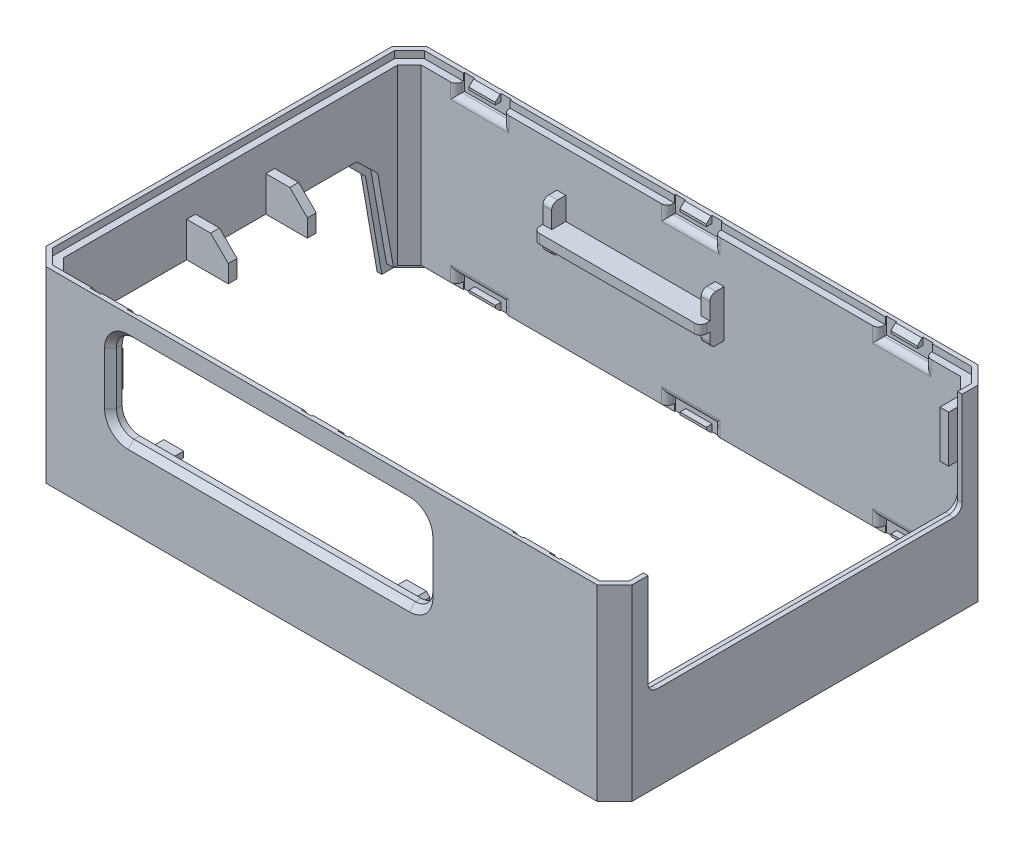
SolidWorks part; units mm, degrees
ref_plane "前视基准面" through (0, 0, 0) normal (0, 0, 1) x (1, 0, 0)
ref_plane "上视基准面" through (0, 0, 0) normal (0, 1, 0) x (1, 0, 0)
ref_plane "右视基准面" through (0, 0, 0) normal (1, 0, 0) x (0, 0, -1)
sketch "草图1" plane through (0, 0, 0) normal (0, 1, 0) x (1, 0, 0)
  line L1 (-50, 32.5) -> (50, 32.5)
  line L2 (-50, 32.5) -> (-50, -32.5)
  line L3 (-50, -32.5) -> (50, -32.5)
  line L4 (50, 32.5) -> (50, -32.5)
  line L5 (-50, 32.5) -> (50, -32.5) construction
  line L6 (-50, -32.5) -> (50, 32.5) construction
  point P0 (0, 0)
  dimension "D1" = 65
  dimension "D2" = 100
extrude "凸台-拉伸1" add sketch "草图1" along normal blind 32
sketch "草图2" plane through (0, 32, 0) normal (0, 1, 0) x (1, 0, 0)
  line L8 (48, -30.5) -> (48, 30.5)
  line L9 (48, 30.5) -> (-48, 30.5)
  line L10 (-48, 30.5) -> (-48, -30.5)
  line L11 (-48, -30.5) -> (48, -30.5)
  line L12 (48, -30.5) -> (48, 30.5)
  line L13 (48, 30.5) -> (-48, 30.5)
  line L14 (-48, 30.5) -> (-48, -30.5)
  line L15 (-48, -30.5) -> (48, -30.5)
  dimension "D1" = 2
extrude "切除-拉伸1" cut sketch "草图2" against normal through all
sketch "草图4" plane through (-50, 0, 0) normal (-1, 0, 0) x (0, 0, 1)
  line L0 (-32.5, 0) -> (32.5, 0) construction
  line L3 (-28, 0) -> (28, 0)
  line L7 (-25.0863, 16.5) -> (-21.5, 20)
  line L8 (21.5, 20) -> (25.09, 16.5)
  line L9 (32.5, 32) -> (32.5, 0) construction
  line L12 (-25.0863, 16.5) -> (-28, 0)
  line L13 (-21.5, 20) -> (21.5, 20)
  line L14 (25.09, 16.5) -> (28, 0)
  line L15 (-32.5, 0) -> (32.5, 0) construction
  line L16 (-32.5, 32) -> (-32.5, 0) construction
  dimension "D1" = 16.5
  dimension "D2" = 20
  dimension "D3" = 4.5
  dimension "D4" = 4.5
  dimension "D5" = 11
  dimension "D6" = 11
  dimension "D7" = 7.4137
  dimension "D8" = 7.41
extrude "切除-拉伸2" cut sketch "草图4" against normal blind 2
sketch "草图7" plane through (0, 0, 32.5) normal (0, 0, 1) x (1, 0, 0)
  line L0 (-50, 32) -> (-50, 0) construction
  line L5 (-50, 32) -> (50, 32) construction
  line L16 (-36, 28) -> (-36, 13)
  line L17 (18, 28) -> (-36, 28)
  line L18 (18, 13) -> (18, 28)
  line L19 (-36, 13) -> (18, 13)
  dimension "D1" = 54
  dimension "D2" = 15
  dimension "D3" = 14
  dimension "D4" = 4
extrude "切除-拉伸3" cut sketch "草图7" against normal blind 2.5
fillet "圆角7" radius 3 4 edges at (-36, 28, 31.5) (18, 28, 31.5) (18, 13, 31.5) (-36, 13, 31.5)
chamfer "倒角1" distance 1 angle 45 8 edges at (-9, 28, 32.5) (-35.1213, 27.1213, 32.5) (17.1213, 27.1213, 32.5) (-36, 20.5, 32.5) (18, 20.5, 32.5) (-35.1213, 13.8787, 32.5) (17.1213, 13.8787, 32.5) (-9, 13, 32.5)
ref_plane "基准面4" through (0, 19.25, 0) normal (0, -1, 0) x (-1, 0, 0)
sketch "草图17" plane through (-48, 0, 0) normal (1, 0, 0) x (0, 0, -1)
  line L1 (-6, 20) -> (-7.5, 20)
  line L2 (-6, 20) -> (-6, 26)
  line L3 (-6, 26) -> (-7.5, 26)
  line L4 (-7.5, 20) -> (-7.5, 26)
  line L5 (32.5, 32) -> (32.5, 0) construction
  line L6 (6, 20) -> (7.5, 20)
  line L7 (6, 20) -> (6, 26)
  line L8 (6, 26) -> (7.5, 26)
  line L9 (7.5, 20) -> (7.5, 26)
  line L10 (-21.5, 20) -> (21.5, 20) construction
  line L12 (-32.5, 32) -> (-32.5, 0) construction
  dimension "D1" = 1.5
  dimension "D2" = 1.5
  dimension "D3" = 25
  dimension "D4" = 25
  dimension "D5" = 6
extrude "凸台-拉伸6" add sketch "草图17" along normal blind 7.1
chamfer "倒角6" distance 3 angle 45 2 edges at (-40.9, 26, -6.75) (-40.9, 26, 6.75)
chamfer "倒角7" distance 2 angle 45 4 edges at (-48, 16, -30.5) (-48, 16, 30.5) (48, 16, -30.5) (48, 16, 30.5)
chamfer "倒角8" distance 3 angle 45 4 edges at (-50, 16, 32.5) (-50, 16, -32.5) (50, 16, -32.5) (50, 16, 32.5)
sketch "草图28" plane through (-50, 0, 0) normal (-1, 0, 0) x (0, 0, 1)
  line L27 (-29.3, 22.3393) -> (-29.3, 0)
  line L28 (-29.3, 0) -> (-26.9872, 0)
  line L29 (-26.9872, 0) -> (-24.2154, 15.8784)
  line L30 (-24.2154, 15.8784) -> (-21.1176, 18.9896)
  line L31 (-21.1176, 18.9896) -> (21.1176, 18.9896)
  line L32 (21.1176, 18.9896) -> (24.2152, 15.8784)
  line L33 (24.2152, 15.8784) -> (27.008, 0)
  line L34 (27.008, 0) -> (29.3, 0)
  line L35 (29.3, 0) -> (29.3, 22.3393)
  line L36 (29.3, 22.3393) -> (-29.3, 22.3393)
  line L37 (28.5, 0) -> (-28.5, 0) construction
  line L38 (-29.5, 0) -> (-28, 0) construction
  line L39 (28, 0) -> (29.5, 0) construction
extrude "凸台-拉伸13" add sketch "草图28" against normal blind 0.8
sketch "草图35" plane through (48, 0, 0) normal (-1, 0, 0) x (0, 0, 1)
  line L0 (-28, 32) -> (28, 32)
  line L1 (-28, 32) -> (-28, 14)
  line L2 (-28, 14) -> (28, 14)
  line L3 (28, 32) -> (28, 14)
  line L4 (32.5, 0) -> (32.5, 32) construction
  line L5 (-32.5, 32) -> (-32.5, 0) construction
  line L6 (28.5, 32) -> (-28.5, 32) construction
  dimension "D1" = 18
  dimension "D3" = 4.5
  dimension "D4" = 4.5
extrude "切除-拉伸6" cut sketch "草图35" against normal blind 1.2
fillet "圆角17" radius 2 2 edges at (48.6, 14, -28) (48.6, 14, 28)
sketch "草图39" plane through (49.2, 0, 0) normal (-1, 0, 0) x (0, 0, 1)
  line L0 (32.5, 0) -> (32.5, 32) construction
  line L1 (-32.5, 32) -> (-32.5, 0) construction
  line L2 (28, 32) -> (-28, 32) construction
  line L3 (29.5, 32) -> (-29.5, 32) construction
  line L4 (29.5, 0) -> (-29.5, 0) construction
  line L12 (-26.8, 32) -> (-26.8, 16)
  line L13 (-25.3, 14.5) -> (25.3, 14.5)
  line L14 (26.8, 16) -> (26.8, 32)
  line L15 (26.8, 32) -> (-26.8, 32)
  arc A6 (-26.8, 16) -> (-25.3, 14.5) centre (-25.3, 16) ccw
  arc A7 (25.3, 14.5) -> (26.8, 16) centre (25.3, 16) ccw
  dimension "D1" = 7.2
  dimension "D2" = 7.2
  dimension "D3" = 16
  dimension "D4" = 14.5
extrude "切除-拉伸7" cut sketch "草图39" against normal blind 1.2
ref_plane "基准面5" through (-50, 32, 29.5) normal (0.7071, 0, 0.7071) x (0.7071, 0, -0.7071)
sketch "草图44" plane through (0, 0, -28) normal (0, 0, 1) x (1, 0, 0)
  line L0 (48, 32) -> (48, 16) construction
  line L1 (48, 28.5) -> (46.5, 28.5)
  line L2 (48, 28.5) -> (48, 20.5)
  line L3 (48, 20.5) -> (46.5, 20.5)
  line L4 (46.5, 28.5) -> (46.5, 20.5)
  line L5 (50, 14.5) -> (49.2, 14.5) construction
  dimension "D1" = 1.5
  dimension "D2" = 8
  dimension "D3" = 6
extrude "凸台-拉伸15" add sketch "草图44" along normal blind 1.5 and the other way up to surface (2.5 mm away) other way up to face at (0, 16, -30.5)
sketch "草图45" plane through (0, 0, 28) normal (0, 0, -1) x (-1, 0, 0)
  line L4 (-48, 28.5) -> (-48, 20.5)
  line L5 (-46.5, 28.5) -> (-48, 28.5)
  line L6 (-46.5, 20.5) -> (-46.5, 28.5)
  line L7 (-48, 20.5) -> (-46.5, 20.5)
  line L8 (-48, 28.5) -> (-48, 20.5)
  line L9 (-46.5, 28.5) -> (-48, 28.5)
  line L10 (-46.5, 20.5) -> (-46.5, 28.5)
  line L11 (-48, 20.5) -> (-46.5, 20.5)
  dimension "D1" = 0
extrude "凸台-拉伸16" add sketch "草图45" along normal blind 1.5 and the other way up to surface (2.5 mm away) other way up to face at (-9, 20.5, 30.5)
ref_plane "基准面6" through (48, 0, -28.5) normal (0, 0, -1) x (-1, 0, 0)
sketch "草图48" plane through (0, 32, 0) normal (0, 1, 0) x (1, 0, 0)
  line L31 (49.2, 29.1686) -> (49.2, -29.1686)
  line L32 (46.6686, -31.7) -> (49.2, -29.1686)
  line L33 (-46.6686, -31.7) -> (46.6686, -31.7)
  line L34 (-49.2, -29.1686) -> (-46.6686, -31.7)
  line L35 (-49.2, 29.1686) -> (-49.2, -29.1686)
  line L36 (-46.6686, 31.7) -> (-49.2, 29.1686)
  line L37 (46.6686, 31.7) -> (-46.6686, 31.7)
  line L38 (49.2, 29.1686) -> (46.6686, 31.7)
  point P0 (48, 30.5)
  point P1 (-48, -30.5)
  point P2 (48, -30.5)
  point P3 (-48, 30.5)
extrude "切除-拉伸8" cut sketch "草图48" against normal blind 1.2
sketch "草图57" plane through (0, 0, 30.5) normal (0, 0, -1) x (-1, 0, 0)
  line L1 (-21.2, 16) -> (-22.7, 16)
  line L2 (-21.2, 16) -> (-21.2, 22)
  line L3 (-21.2, 22) -> (-22.7, 22)
  line L4 (-22.7, 16) -> (-22.7, 22)
  line L5 (39.4, 16) -> (40.9, 16)
  line L6 (39.4, 16) -> (39.4, 22)
  line L7 (39.4, 22) -> (40.9, 22)
  line L8 (40.9, 16) -> (40.9, 22)
  line L9 (47, 32) -> (-47, 32) construction
  line L10 (-50, 32) -> (-50, 0) construction
  line L11 (50, 0) -> (50, 32) construction
  line L12 (46, 0) -> (-46, 0) construction
  line L17 (-14, 12) -> (-10, 12)
  line L18 (-14, 12) -> (-14, 11)
  line L19 (-14, 11) -> (-10, 11)
  line L20 (-10, 12) -> (-10, 11)
  line L21 (28, 12) -> (32, 12)
  line L22 (28, 12) -> (28, 11)
  line L23 (28, 11) -> (32, 11)
  line L24 (32, 12) -> (32, 11)
  dimension "D1" = 1.5
  dimension "D2" = 16
  dimension "D3" = 28.8
  dimension "D4" = 10.6
  dimension "D5" = 4
  dimension "D6" = 4
  dimension "D7" = 1
  dimension "D8" = 1
  dimension "D9" = 12
  dimension "D10" = 18
  dimension "D11" = 60
  dimension "D12" = 6
extrude "凸台-拉伸27" add sketch "草图57" along normal blind 2.5
sketch "草图60" plane through (21.2, 0, 0) normal (-1, 0, 0) x (0, 0, 1)
  line L0 (28, 22) -> (30.5, 22) construction
  line L1 (28, 22) -> (29.25, 22)
  line L2 (28, 22) -> (28, 16)
  line L3 (28, 16) -> (29.25, 16)
  line L4 (29.25, 22) -> (29.25, 16)
  line L5 (28, 16) -> (30.5, 16) construction
  dimension "D1" = 1.25
extrude "凸台-拉伸28" add sketch "草图60" along normal blind 1
sketch "草图61" plane through (-39.4, 0, 0) normal (1, 0, 0) x (0, 0, -1)
  line L4 (-28, 16) -> (-28, 22)
  line L5 (-29.25, 16) -> (-28, 16)
  line L6 (-29.25, 22) -> (-29.25, 16)
  line L7 (-28, 22) -> (-29.25, 22)
  line L8 (-28, 16) -> (-28, 22)
  line L9 (-29.25, 16) -> (-28, 16)
  line L10 (-29.25, 22) -> (-29.25, 16)
  line L11 (-28, 22) -> (-29.25, 22)
  dimension "D1" = 0
extrude "凸台-拉伸29" add sketch "草图61" along normal blind 1
chamfer "倒角16" distance 0.6 angle 45 2 edges at (14, 12, 29.25) (-32, 12, 29.25)
sketch "草图62" plane through (0, 0, 0) normal (0, -1, 0) x (1, 0, 0)
  line L15 (-49.2, 28.9971) -> (-49.2, -28.9971)
  line L16 (-46.4971, -31.7) -> (-49.2, -28.9971)
  line L17 (46.4971, -31.7) -> (-46.4971, -31.7)
  line L18 (49.2, -28.9971) -> (46.4971, -31.7)
  line L19 (49.2, 28.9971) -> (49.2, -28.9971)
  line L20 (46.4971, 31.7) -> (49.2, 28.9971)
  line L21 (-46.4971, 31.7) -> (46.4971, 31.7)
  line L22 (-49.2, 28.9971) -> (-46.4971, 31.7)
extrude "切除-拉伸9" cut sketch "草图62" against normal blind 1.2 contours L15 L16 L17 L18 L19 L20 L21 L22
sketch "草图63" plane through (0, 0, -30.5) normal (0, 0, 1) x (1, 0, 0)
  line L1 (-22.8279, 18.4) -> (5.6721, 18.4)
  line L2 (-22.8279, 18.4) -> (-22.8279, 20)
  line L3 (-22.8279, 20) -> (5.6721, 20)
  line L4 (5.6721, 18.4) -> (5.6721, 20)
extrude "凸台-拉伸30" add sketch "草图63" along normal blind 4
sketch "草图64" plane through (0, 0, -30.5) normal (0, 0, 1) x (1, 0, 0)
  line L1 (-22.8279, 15.8832) -> (-21.3279, 15.8832)
  line L2 (-22.8279, 15.8832) -> (-22.8279, 23.8832)
  line L3 (-22.8279, 23.8832) -> (-21.3279, 23.8832)
  line L4 (-21.3279, 15.8832) -> (-21.3279, 23.8832)
  line L5 (4.1721, 15.8832) -> (5.6721, 15.8832)
  line L6 (4.1721, 15.8832) -> (4.1721, 23.8832)
  line L7 (4.1721, 23.8832) -> (5.6721, 23.8832)
  line L8 (5.6721, 15.8832) -> (5.6721, 23.8832)
extrude "凸台-拉伸31" add sketch "草图64" along normal blind 2.4
fillet "圆角18" radius 1 6 edges at (-22.8279, 19.2, -26.5) (5.6721, 19.2, -26.5) (4.9221, 15.8832, -28.1) (-22.0779, 15.8832, -28.1) (4.9221, 23.8832, -28.1) (-22.0779, 23.8832, -28.1)
sketch "草图65" plane through (0, 0, -30.5) normal (0, 0, 1) x (1, 0, 0)
  line L0 (-47, 32) -> (47, 32) construction
  line L1 (32, 32) -> (40, 32)
  line L2 (32, 32) -> (32, 29.2)
  line L3 (32, 29.2) -> (40, 29.2)
  line L4 (40, 32) -> (40, 29.2)
  line L5 (50, 32) -> (50, 0) construction
  line L7 (-4, 32) -> (4, 32)
  line L8 (-4, 32) -> (-4, 29.2)
  line L9 (-4, 29.2) -> (4, 29.2)
  line L10 (4, 32) -> (4, 29.2)
  line L12 (-40, 32) -> (-32, 32)
  line L13 (-40, 32) -> (-40, 29.2)
  line L14 (-40, 29.2) -> (-32, 29.2)
  line L15 (-32, 32) -> (-32, 29.2)
  line L16 (-40, 0) -> (-32, 0)
  line L17 (-40, 0) -> (-40, 2.8)
  line L18 (-40, 2.8) -> (-32, 2.8)
  line L19 (-32, 0) -> (-32, 2.8)
  line L20 (-4, 0) -> (4, 0)
  line L21 (-4, 0) -> (-4, 2.8)
  line L22 (-4, 2.8) -> (4, 2.8)
  line L23 (4, 0) -> (4, 2.8)
  line L24 (32, 0) -> (40, 0)
  line L25 (32, 0) -> (32, 2.8)
  line L26 (32, 2.8) -> (40, 2.8)
  line L27 (40, 0) -> (40, 2.8)
  dimension "D1" = 2.8
  dimension "D2" = 10
  dimension "D3" = 8
  dimension "D6" = 28
  dimension "D7" = 28
extrude "切除-拉伸10" cut sketch "草图65" against normal blind 1.4
sketch "草图67" plane through (0, 0, 30.5) normal (0, 0, -1) x (-1, 0, 0)
  line L4 (4, 32) -> (-4, 32)
  line L5 (-4, 32) -> (-4, 29.2)
  line L6 (-4, 29.2) -> (4, 29.2)
  line L7 (4, 29.2) -> (4, 32)
  line L8 (4, 32) -> (-4, 32)
  line L9 (-4, 32) -> (-4, 29.2)
  line L10 (-4, 29.2) -> (4, 29.2)
  line L11 (4, 29.2) -> (4, 32)
  line L12 (-32, 32) -> (-40, 32)
  line L13 (-40, 32) -> (-40, 29.2)
  line L14 (-40, 29.2) -> (-32, 29.2)
  line L15 (-32, 29.2) -> (-32, 32)
  line L16 (-32, 32) -> (-40, 32)
  line L17 (-40, 32) -> (-40, 29.2)
  line L18 (-40, 29.2) -> (-32, 29.2)
  line L19 (-32, 29.2) -> (-32, 32)
  line L20 (-40, 0) -> (-32, 0)
  line L21 (-40, 2.8) -> (-40, 0)
  line L22 (-32, 2.8) -> (-40, 2.8)
  line L23 (-32, 0) -> (-32, 2.8)
  line L24 (-40, 0) -> (-32, 0)
  line L25 (-40, 2.8) -> (-40, 0)
  line L26 (-32, 2.8) -> (-40, 2.8)
  line L27 (-32, 0) -> (-32, 2.8)
  line L28 (-4, 0) -> (4, 0)
  line L29 (-4, 2.8) -> (-4, 0)
  line L30 (4, 2.8) -> (-4, 2.8)
  line L31 (4, 0) -> (4, 2.8)
  line L32 (-4, 0) -> (4, 0)
  line L33 (-4, 2.8) -> (-4, 0)
  line L34 (4, 2.8) -> (-4, 2.8)
  line L35 (4, 0) -> (4, 2.8)
  line L36 (32, 0) -> (40, 0)
  line L37 (40, 0) -> (40, 2.8)
  line L38 (40, 2.8) -> (32, 2.8)
  line L39 (32, 2.8) -> (32, 0)
  line L40 (32, 0) -> (40, 0)
  line L41 (40, 0) -> (40, 2.8)
  line L42 (40, 2.8) -> (32, 2.8)
  line L43 (32, 2.8) -> (32, 0)
  line L44 (40, 32) -> (32, 32)
  line L45 (40, 29.2) -> (40, 32)
  line L46 (32, 29.2) -> (40, 29.2)
  line L47 (32, 32) -> (32, 29.2)
  line L48 (40, 32) -> (32, 32)
  line L49 (40, 29.2) -> (40, 32)
  line L50 (32, 29.2) -> (40, 29.2)
  line L51 (32, 32) -> (32, 29.2)
  dimension "D1" = 0
  dimension "D2" = 0
  dimension "D3" = 0
  dimension "D4" = 0
  dimension "D5" = 0
  dimension "D6" = 0
extrude "切除-拉伸11" cut sketch "草图67" against normal blind 1.4
fillet "圆角19" radius 1 36 edges at (-32, 30, -30.5) (-36, 29.2, -30.5) (-40, 30, -30.5) (40, 30, -30.5) (36, 29.2, -30.5) (32, 30, -30.5) (4, 30, -30.5) (0, 29.2, -30.5) (-4, 30, -30.5) (-40, 30, 30.5) (-36, 29.2, 30.5) (-32, 30, 30.5) (-4, 30, 30.5) (0, 29.2, 30.5) (4, 30, 30.5) (32, 30, 30.5) (40, 30, 30.5) (36, 29.2, 30.5) (4, 2, 30.5) (-4, 2, 30.5) (0, 2.8, 30.5) (40, 2, 30.5) (32, 2, 30.5) (36, 2.8, 30.5) (-36, 2.8, 30.5) (-32, 2, 30.5) (-40, 2, 30.5) (40, 2, -30.5) (32, 2, -30.5) (36, 2.8, -30.5) (-4, 2, -30.5) (4, 2, -30.5) (0, 2.8, -30.5) (-36, 2.8, -30.5) (-32, 2, -30.5) (-40, 2, -30.5)
sketch "草图70" plane through (0, 0, -31.9) normal (0, 0, 1) x (1, 0, 0)
  line L0 (-32, 32) -> (-40, 32) construction
  line L1 (-38.25, 32) -> (-33.75, 32)
  line L2 (-38.25, 32) -> (-38.25, 30.8)
  line L3 (-38.25, 30.8) -> (-33.75, 30.8)
  line L4 (-33.75, 32) -> (-33.75, 30.8)
  line L5 (-38.25, 32) -> (-33.75, 30.8) construction
  line L6 (-38.25, 30.8) -> (-33.75, 32) construction
  line L7 (-2.25, 32) -> (2.25, 32)
  line L8 (-2.25, 32) -> (-2.25, 30.8)
  line L9 (-2.25, 30.8) -> (2.25, 30.8)
  line L10 (2.25, 32) -> (2.25, 30.8)
  line L11 (-2.25, 32) -> (2.25, 30.8) construction
  line L12 (-2.25, 30.8) -> (2.25, 32) construction
  line L13 (33.75, 32) -> (38.25, 32)
  line L14 (33.75, 32) -> (33.75, 30.8)
  line L15 (33.75, 30.8) -> (38.25, 30.8)
  line L16 (38.25, 32) -> (38.25, 30.8)
  line L17 (33.75, 32) -> (38.25, 30.8) construction
  line L18 (33.75, 30.8) -> (38.25, 32) construction
  line L19 (4, 32) -> (-4, 32) construction
  line L20 (40, 32) -> (32, 32) construction
  line L21 (47, 32) -> (-47, 32) construction
  line L22 (-40, 0) -> (-32, 0) construction
  line L23 (33.75, 1.2) -> (38.25, 1.2)
  line L24 (33.75, 1.2) -> (33.75, 0)
  line L25 (33.75, 0) -> (38.25, 0)
  line L26 (38.25, 1.2) -> (38.25, 0)
  line L27 (33.75, 1.2) -> (38.25, 0) construction
  line L28 (33.75, 0) -> (38.25, 1.2) construction
  line L29 (-2.25, 1.2) -> (2.25, 1.2)
  line L30 (-2.25, 1.2) -> (-2.25, 0)
  line L31 (-2.25, 0) -> (2.25, 0)
  line L32 (2.25, 1.2) -> (2.25, 0)
  line L33 (-2.25, 1.2) -> (2.25, 0) construction
  line L34 (-2.25, 0) -> (2.25, 1.2) construction
  line L35 (-38.25, 1.2) -> (-33.75, 1.2)
  line L36 (-38.25, 1.2) -> (-38.25, 0)
  line L37 (-38.25, 0) -> (-33.75, 0)
  line L38 (-33.75, 1.2) -> (-33.75, 0)
  line L39 (-38.25, 1.2) -> (-33.75, 0) construction
  line L40 (-38.25, 0) -> (-33.75, 1.2) construction
  point P0 (-36, 31.4)
  point P5 (0, 31.4)
  point P10 (36, 31.4)
  point P15 (0, 0.6)
  point P18 (-36, 32)
  point P22 (0, 32)
  point P26 (36, 32)
  point P29 (-36, 0.6)
  point P35 (36, 0.6)
  dimension "D1" = 4.5
  dimension "D2" = 1.2
  dimension "D3" = 0
  dimension "D4" = 0
extrude "凸台-拉伸32" add sketch "草图70" along normal blind 1
sketch "草图71" plane through (0, 0, 31.9) normal (0, 0, -1) x (-1, 0, 0)
  line L0 (-38.25, 0) -> (-38.25, 1.2) construction
  line L1 (-38.25, 1.2) -> (-33.75, 1.2) construction
  line L2 (-33.75, 1.2) -> (-33.75, 0) construction
  line L3 (-33.75, 0) -> (-38.25, 0) construction
  line L4 (-2.25, 0) -> (-2.25, 1.2) construction
  line L5 (-2.25, 1.2) -> (2.25, 1.2) construction
  line L6 (2.25, 1.2) -> (2.25, 0) construction
  line L7 (2.25, 0) -> (-2.25, 0) construction
  line L8 (33.75, 0) -> (33.75, 1.2) construction
  line L9 (33.75, 1.2) -> (38.25, 1.2) construction
  line L10 (38.25, 1.2) -> (38.25, 0) construction
  line L11 (38.25, 0) -> (33.75, 0) construction
  line L12 (33.75, 30.8) -> (33.75, 32) construction
  line L13 (33.75, 32) -> (38.25, 32) construction
  line L14 (38.25, 32) -> (38.25, 30.8) construction
  line L15 (38.25, 30.8) -> (33.75, 30.8) construction
  line L16 (-2.25, 30.8) -> (-2.25, 32) construction
  line L17 (-2.25, 32) -> (2.25, 32) construction
  line L18 (2.25, 32) -> (2.25, 30.8) construction
  line L19 (2.25, 30.8) -> (-2.25, 30.8) construction
  line L20 (-38.25, 30.8) -> (-38.25, 32) construction
  line L21 (-38.25, 32) -> (-33.75, 32) construction
  line L22 (-33.75, 32) -> (-33.75, 30.8) construction
  line L23 (-33.75, 30.8) -> (-38.25, 30.8) construction
  line L24 (-38.25, 0) -> (-38.25, 1.2)
  line L25 (-38.25, 1.2) -> (-33.75, 1.2)
  line L26 (-33.75, 1.2) -> (-33.75, 0)
  line L27 (-33.75, 0) -> (-38.25, 0)
  line L28 (-2.25, 0) -> (-2.25, 1.2)
  line L29 (-2.25, 1.2) -> (2.25, 1.2)
  line L30 (2.25, 1.2) -> (2.25, 0)
  line L31 (2.25, 0) -> (-2.25, 0)
  line L32 (33.75, 0) -> (33.75, 1.2)
  line L33 (33.75, 1.2) -> (38.25, 1.2)
  line L34 (38.25, 1.2) -> (38.25, 0)
  line L35 (38.25, 0) -> (33.75, 0)
  line L36 (33.75, 30.8) -> (33.75, 32)
  line L37 (33.75, 32) -> (38.25, 32)
  line L38 (38.25, 32) -> (38.25, 30.8)
  line L39 (38.25, 30.8) -> (33.75, 30.8)
  line L40 (-2.25, 30.8) -> (-2.25, 32)
  line L41 (-2.25, 32) -> (2.25, 32)
  line L42 (2.25, 32) -> (2.25, 30.8)
  line L43 (2.25, 30.8) -> (-2.25, 30.8)
  line L44 (-38.25, 30.8) -> (-38.25, 32)
  line L45 (-38.25, 32) -> (-33.75, 32)
  line L46 (-33.75, 32) -> (-33.75, 30.8)
  line L47 (-33.75, 30.8) -> (-38.25, 30.8)
extrude "凸台-拉伸33" add sketch "草图71" along normal blind 1
chamfer "倒角17" distance 0.8 angle 45 12 edges at (36, 0, -30.9) (0, 0, -30.9) (-36, 0, -30.9) (36, 0, 30.9) (0, 0, 30.9) (-36, 0, 30.9) (-36, 32, 30.9) (0, 32, 30.9) (36, 32, 30.9) (-36, 32, -30.9) (0, 32, -30.9) (36, 32, -30.9)
